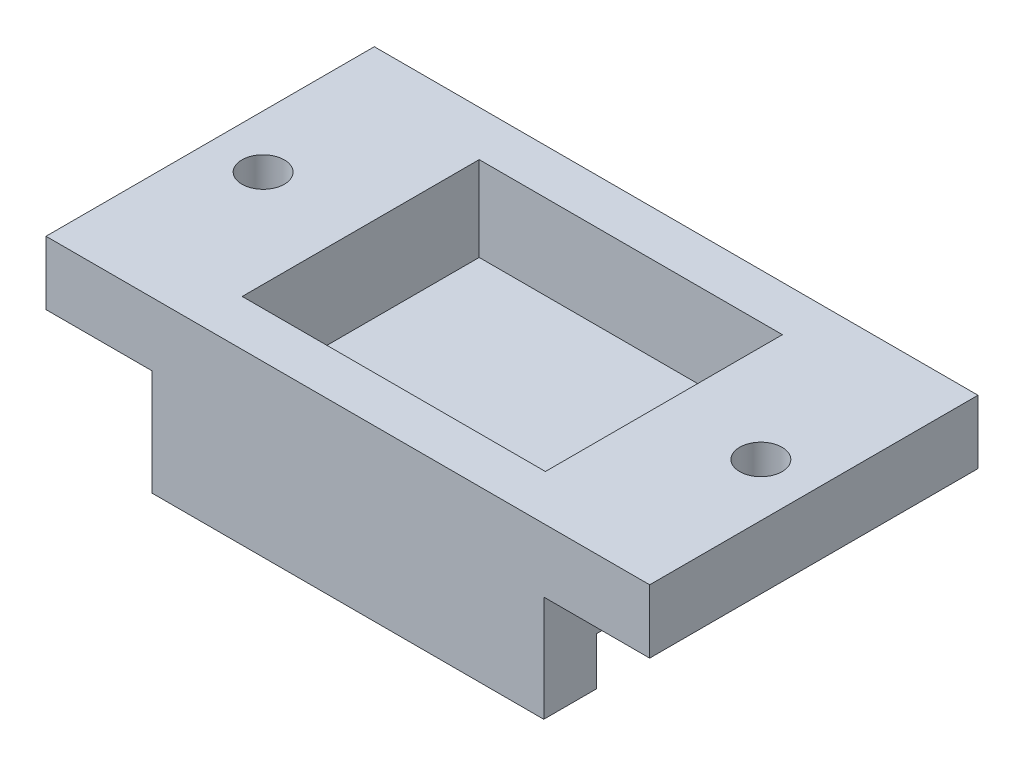
SolidWorks part; units mm, degrees
ref_plane "Front Plane" through (0, 0, 0) normal (0, 0, 1) x (1, 0, 0)
ref_plane "Top Plane" through (0, 0, 0) normal (0, 1, 0) x (1, 0, 0)
ref_plane "Right Plane" through (0, 0, 0) normal (1, 0, 0) x (0, 0, -1)
sketch "Sketch2" plane through (0, 0, 0) normal (0, 1, 0) x (1, 0, 0)
  line L1 (-12.8729, 6.7833) -> (5.6271, 6.7833)
  line L2 (-12.8729, 6.7833) -> (-12.8729, -8.7167)
  line L3 (-12.8729, -8.7167) -> (5.6271, -8.7167)
  line L4 (5.6271, 6.7833) -> (5.6271, -8.7167)
  line L5 (-12.8729, 6.7833) -> (5.6271, -8.7167) construction
  line L6 (-12.8729, -8.7167) -> (5.6271, 6.7833) construction
  point P0 (-3.6229, -0.9667)
  dimension "D1" = 18.5
  dimension "D2" = 15.5
extrude "Boss-Extrude1" add sketch "Sketch2" along normal blind 11
sketch "Sketch3" plane through (0, 11, 0) normal (0, 1, 0) x (1, 0, 0)
  line L1 (-12.8729, 6.7833) -> (5.6271, 6.7833)
  line L2 (-12.8729, 6.7833) -> (-12.8729, -8.7167)
  line L3 (-12.8729, -8.7167) -> (5.6271, -8.7167)
  line L4 (5.6271, 6.7833) -> (5.6271, -8.7167)
extrude "Boss-Extrude2" add sketch "Sketch3" along normal blind 3
sketch "Sketch4" plane through (0, 14, 0) normal (0, 1, 0) x (1, 0, 0)
  line L0 (5.6271, 6.7833) -> (-12.8729, 6.7833) construction
  line L1 (-10.3729, 4.2833) -> (3.1271, 4.2833)
  line L2 (-10.3729, 4.2833) -> (-10.3729, -6.2167)
  line L3 (-10.3729, -6.2167) -> (3.1271, -6.2167)
  line L4 (3.1271, 4.2833) -> (3.1271, -6.2167)
  line L5 (5.6271, -8.7167) -> (5.6271, 6.7833) construction
  dimension "D1" = 10.5
  dimension "D2" = 13.5
  dimension "D3" = 2.5
  dimension "D4" = 2.5
extrude "Cut-Extrude1" cut sketch "Sketch4" against normal blind 6
sketch "Sketch5" plane through (0, 8, 0) normal (0, 1, 0) x (1, 0, 0)
  line L0 (-10.3729, -6.2167) -> (3.1271, -6.2167) construction
  line L1 (3.1271, 4.2833) -> (0.1271, 4.2833)
  line L2 (3.1271, 4.2833) -> (3.1271, -6.2167)
  line L3 (3.1271, -6.2167) -> (0.1271, -6.2167)
  line L4 (0.1271, 4.2833) -> (0.1271, -6.2167)
  dimension "D1" = 3
extrude "Cut-Extrude2" cut sketch "Sketch5" against normal blind 26 contours L4 L3 L2 L1
sketch "Sketch10" plane through (0, 0, 8.7167) normal (0, 0, 1) x (1, 0, 0)
  line L0 (5.6271, 14) -> (5.6271, 0) construction
  line L1 (-12.8729, 0) -> (5.6271, 0)
  line L2 (-12.8729, 0) -> (-12.8729, 5)
  line L3 (-12.8729, 5) -> (5.6271, 5)
  line L4 (5.6271, 0) -> (5.6271, 5)
  dimension "D1" = 5
extrude "Cut-Extrude3" cut sketch "Sketch10" against normal blind 26
sketch "Sketch11" plane through (5.6271, 0, 0) normal (1, 0, 0) x (0, 0, -1)
  line L0 (6.7833, 14) -> (6.7833, 5) construction
  line L1 (-8.7167, 14) -> (6.7833, 14)
  line L2 (-8.7167, 14) -> (-8.7167, 11)
  line L3 (-8.7167, 11) -> (6.7833, 11)
  line L4 (6.7833, 14) -> (6.7833, 11)
  dimension "D1" = 3
extrude "Boss-Extrude3" add sketch "Sketch11" along normal blind 5
sketch "Sketch13" plane through (0, 5, 0) normal (0, -1, 0) x (1, 0, 0)
  line L0 (-12.8729, -6.7833) -> (-12.8729, 8.7167) construction
  line L1 (5.6271, 8.7167) -> (-12.8729, 8.7167)
  line L2 (5.6271, 8.7167) -> (5.6271, 6.2179)
  line L3 (5.6271, 6.2179) -> (-12.8729, 6.2179)
  line L4 (-12.8729, 8.7167) -> (-12.8729, 6.2179)
  line L6 (5.6271, -6.7833) -> (-12.8729, -6.7833)
  line L7 (5.6271, -6.7833) -> (5.6271, -4.2846)
  line L8 (5.6271, -4.2846) -> (-12.8729, -4.2846)
  line L9 (-12.8729, -6.7833) -> (-12.8729, -4.2846)
  line L10 (-12.8729, 6.2179) -> (0.1271, 6.2179)
  line L11 (-12.8729, 6.2179) -> (-12.8729, -4.2833)
  line L12 (-12.8729, -4.2833) -> (0.1271, -4.2833)
  line L13 (0.1271, 6.2179) -> (0.1271, -4.2833)
  line M1 (0.1271, -4.2833) -> (0.1271, 6.2167)
  line M5 (5.6271, -6.7833) -> (5.6271, 8.7167)
  line M6 (5.6271, 8.7167) -> (-12.8729, 8.7167)
  line M7 (-12.8729, 8.7167) -> (-12.8729, -6.7833)
  line M8 (-12.8729, -6.7833) -> (5.6271, -6.7833)
extrude "Boss-Extrude4" add sketch "Sketch13" along normal blind 3 contours L3 M5 M6 M7 | L13 L3 L12 M7 M1 | L8 M5 M7 M8 region at (-3.6229, 5, 7.4673) region at (-6.3729, 5, 0.9673) region at (-3.6229, 5, -5.5339)
sketch "Sketch14" plane through (-12.8729, 0, 0) normal (-1, 0, 0) x (0, 0, 1)
  line L0 (8.7167, 14) -> (8.7167, 2) construction
  line L1 (-6.7833, 14) -> (8.7167, 14)
  line L2 (-6.7833, 14) -> (-6.7833, 11)
  line L3 (-6.7833, 11) -> (8.7167, 11)
  line L4 (8.7167, 14) -> (8.7167, 11)
  dimension "D1" = 3
extrude "Boss-Extrude6" add sketch "Sketch14" along normal blind 5 contours L3 L4 L1 L2
sketch "Sketch16" plane through (0, 14, 0) normal (0, 1, 0) x (1, 0, 0)
  line L0 (-17.8729, 6.7833) -> (-17.8729, -8.7167) construction
  line L1 (10.6271, 6.7833) -> (10.6271, -8.7167) construction
  circle A0 centre (-15.3729, -0.9667) radius 1
  circle A1 centre (8.1271, -0.9667) radius 1
  dimension "D1" = 2
  dimension "D2" = 2.5
  dimension "D3" = 2
  dimension "D4" = 2.5
extrude "Cut-Extrude5" cut sketch "Sketch16" against normal blind 5 contours A0 | A1
sketch "Sketch18" plane through (0, 14, 0) normal (0, 1, 0) x (1, 0, 0)
  line L1 (-10.7802, 4.6423) -> (3.5344, 4.6423)
  line L2 (-10.7802, 4.6423) -> (-10.7802, -6.5464)
  line L3 (-10.7802, -6.5464) -> (3.5344, -6.5464)
  line L4 (3.5344, 4.6423) -> (3.5344, -6.5464)
extrude "Cut-Extrude6" cut sketch "Sketch18" against normal blind 6
sketch "Sketch19" plane through (5.6271, 0, 0) normal (1, 0, 0) x (0, 0, -1)
  line L0 (4.2846, 2) -> (4.2846, 5) construction
  line L1 (-6.2179, 5) -> (4.2863, 5)
  line L2 (-6.2179, 5) -> (-6.2179, 8.2547)
  line L3 (-6.2179, 8.2547) -> (4.2863, 8.2547)
  line L4 (4.2863, 5) -> (4.2863, 8.2547)
  dimension "D1" = 0.0017
extrude "Cut-Extrude7" cut sketch "Sketch19" against normal blind 2.5 contours L3 L4 L1 L2
sketch "Sketch20" plane through (0, 8, 0) normal (0, 1, 0) x (1, 0, 0)
  line L0 (-10.7802, -6.5464) -> (3.5344, -6.5464) construction
  line L1 (-10.7802, 4.6423) -> (0.1271, 4.6423)
  line L2 (-10.7802, 4.6423) -> (-10.7802, -6.5464)
  line L3 (-10.7802, -6.5464) -> (0.1271, -6.5464)
  line L4 (0.1271, 4.6423) -> (0.1271, -6.5464)
extrude "Boss-Extrude7" add sketch "Sketch20" along normal blind 2
sketch "Sketch23" plane through (0, 0, 8.7167) normal (0, 0, 1) x (1, 0, 0)
  line L0 (5.6271, 11) -> (5.6271, 2) construction
  line L1 (-12.8729, 2) -> (5.6271, 2)
  line L2 (-12.8729, 2) -> (-12.8729, 6)
  line L3 (-12.8729, 6) -> (5.6271, 6)
  line L4 (5.6271, 2) -> (5.6271, 6)
  dimension "D1" = 4
extrude "Cut-Extrude8" cut sketch "Sketch23" against normal blind 22
